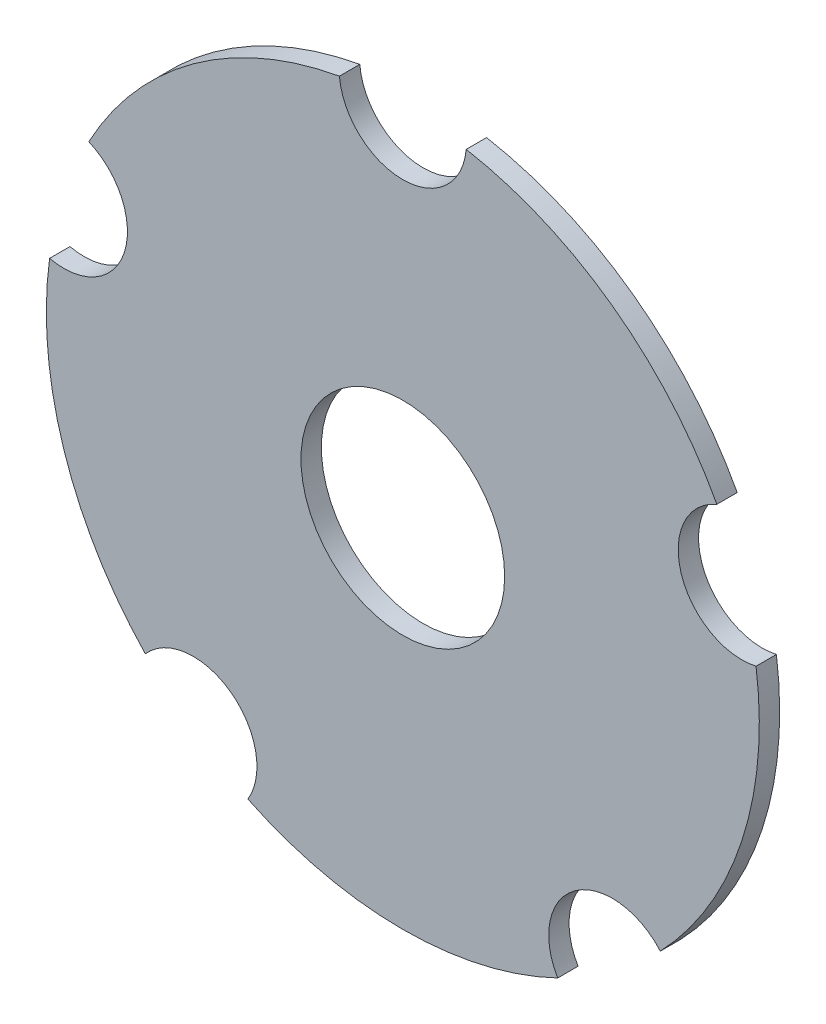
SolidWorks part; units mm, degrees
ref_plane "Front Plane" through (0, 0, 0) normal (0, 0, 1) x (1, 0, 0)
ref_plane "Top Plane" through (0, 0, 0) normal (0, 1, 0) x (1, 0, 0)
ref_plane "Right Plane" through (0, 0, 0) normal (1, 0, 0) x (0, 0, -1)
sketch "Sketch2" plane through (0, 0, 0) normal (0, 0, 1) x (1, 0, 0)
  arc A14 (-6.225, 34.442) -> (-30.8326, 16.5635) centre (0, 0) ccw
  arc A15 (-6.225, 34.442) -> (6.225, 34.442) centre (0, 35) ccw
  arc A16 (30.8326, 16.5635) -> (34.6799, 4.7228) centre (33.287, 10.8156) ccw
  arc A17 (25.2806, -24.2051) -> (15.2083, -31.5231) centre (20.5725, -28.3156) ccw
  arc A18 (-15.2083, -31.5231) -> (-25.2806, -24.2051) centre (-20.5725, -28.3156) ccw
  arc A19 (-34.6799, 4.7228) -> (-30.8326, 16.5635) centre (-33.287, 10.8156) ccw
  arc A20 (-34.6799, 4.7228) -> (-25.2806, -24.2051) centre (0, 0) ccw
  arc A21 (-15.2083, -31.5231) -> (15.2083, -31.5231) centre (0, 0) ccw
  arc A22 (25.2806, -24.2051) -> (34.6799, 4.7228) centre (0, 0) ccw
  arc A23 (30.8326, 16.5635) -> (6.225, 34.442) centre (0, 0) ccw
  circle A24 centre (0, 0) radius 10
  dimension "D1" = 70
  dimension "D2" = 12.5
  dimension "D4" = 20
  dimension "D3" = 5
extrude "Boss-Extrude2" add sketch "Sketch2" along normal blind 2
